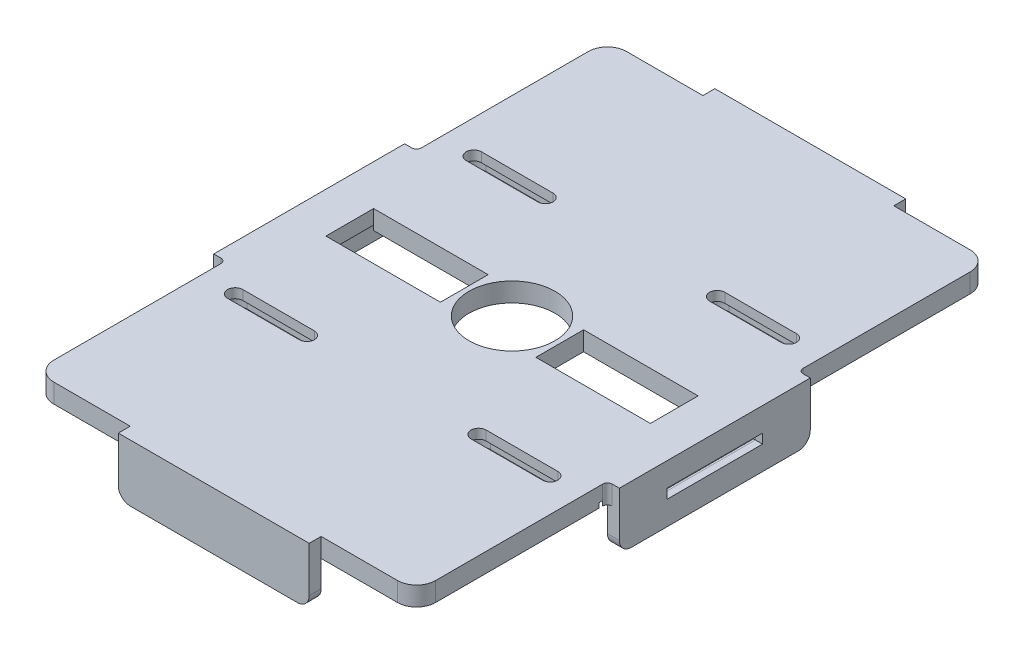
SolidWorks part; units mm, degrees
ref_plane "Front Plane" through (0, 0, 0) normal (0, 0, 1) x (1, 0, 0)
ref_plane "Top Plane" through (0, 0, 0) normal (0, 1, 0) x (1, 0, 0)
ref_plane "Right Plane" through (0, 0, 0) normal (1, 0, 0) x (0, 0, -1)
sketch "Sketch2" plane through (0, 40.2308, 0) normal (0, -1, 0) x (1, 0, 0)
  line L0 (-24.885, -26.4079) -> (-39.885, -26.4079) construction
  line L1 (-39.885, -23.2079) -> (-24.885, -23.2079) construction
  line L2 (-24.885, 23.5921) -> (-39.885, 23.5921) construction
  line L3 (-39.885, 26.7921) -> (-24.885, 26.7921) construction
  line L6 (-24.885, -26.4079) -> (-39.885, -26.4079)
  line L7 (-39.885, -23.2079) -> (-24.885, -23.2079)
  line L8 (-24.885, 23.5921) -> (-39.885, 23.5921)
  line L9 (-39.885, 26.7921) -> (-24.885, 26.7921)
  line L12 (-6.885, 34.7921) -> (-6.885, -34.4079) construction
  line L15 (26.115, 26.7921) -> (11.115, 26.7921)
  line L16 (11.115, 23.5921) -> (26.115, 23.5921)
  line L17 (26.115, -23.2079) -> (11.115, -23.2079)
  line L18 (11.115, -26.4079) -> (26.115, -26.4079)
  line L20 (-46.885, -59.8079) -> (33.115, -59.8079)
  line L21 (-46.885, -59.8079) -> (-46.885, 60.1921)
  line L22 (-46.885, 60.1921) -> (33.115, 60.1921)
  line L23 (33.115, -59.8079) -> (33.115, 60.1921)
  line L24 (-46.885, -59.8079) -> (33.115, 60.1921) construction
  line L25 (-46.885, 60.1921) -> (33.115, -59.8079) construction
  arc A0 (-6.885, 9.1921) -> (-6.885, -8.8079) centre (-6.885, 0.1921) ccw construction
  arc A1 (-24.885, -26.4079) -> (-24.885, -23.2079) centre (-24.885, -24.8079) ccw construction
  arc A2 (-39.885, -23.2079) -> (-39.885, -26.4079) centre (-39.885, -24.8079) ccw construction
  arc A3 (-24.885, 23.5921) -> (-24.885, 26.7921) centre (-24.885, 25.1921) ccw construction
  arc A4 (-39.885, 26.7921) -> (-39.885, 23.5921) centre (-39.885, 25.1921) ccw construction
  circle A7 centre (-6.885, 0.1921) radius 9
  arc A8 (-24.885, -26.4079) -> (-24.885, -23.2079) centre (-24.885, -24.8079) ccw
  arc A9 (-39.885, -23.2079) -> (-39.885, -26.4079) centre (-39.885, -24.8079) ccw
  arc A10 (-24.885, 23.5921) -> (-24.885, 26.7921) centre (-24.885, 25.1921) ccw
  arc A11 (-39.885, 26.7921) -> (-39.885, 23.5921) centre (-39.885, 25.1921) ccw
  arc A14 (-5.285, 33.1921) -> (-8.485, 33.1921) centre (-6.885, 33.1921) ccw construction
  arc A17 (26.115, 26.7921) -> (26.115, 23.5921) centre (26.115, 25.1921) cw
  arc A18 (11.115, 23.5921) -> (11.115, 26.7921) centre (11.115, 25.1921) cw
  arc A19 (26.115, -23.2079) -> (26.115, -26.4079) centre (26.115, -24.8079) cw
  arc A20 (11.115, -26.4079) -> (11.115, -23.2079) centre (11.115, -24.8079) cw
  dimension "D1" = 80
  dimension "D2" = 120
extrude "Boss-Extrude1" add sketch "Sketch2" along normal blind 4
fillet "Fillet1" radius 4 4 edges at (-46.885, 38.2308, 60.1921) (33.115, 38.2308, 60.1921) (33.115, 38.2308, -59.8079) (-46.885, 38.2308, -59.8079)
sketch "Sketch3" plane through (0, 36.2308, 0) normal (0, -1, 0) x (1, 0, 0)
  line L3 (-6.885, 60.1921) -> (-6.885, -59.8079) construction
  line L4 (29.115, 60.1921) -> (-42.885, 60.1921) construction
  line L5 (-42.885, -59.8079) -> (29.115, -59.8079) construction
  line L6 (-46.885, 0.1921) -> (33.115, 0.1921) construction
  line L7 (-26.885, 60.1921) -> (13.115, 60.1921)
  line L8 (-26.885, 60.1921) -> (-26.885, 62.6921)
  line L9 (-26.885, 62.6921) -> (13.115, 62.6921)
  line L10 (13.115, 60.1921) -> (13.115, 62.6921)
  line L11 (-26.885, 60.1921) -> (13.115, 62.6921) construction
  line L12 (-26.885, 62.6921) -> (13.115, 60.1921) construction
  line L17 (-46.885, 56.1921) -> (-46.885, -55.8079) construction
  line L18 (33.115, -55.8079) -> (33.115, 56.1921) construction
  point P12 (-6.885, 61.4421)
  dimension "D1" = 2.5
  dimension "D2" = 40
extrude "Boss-Extrude3" add sketch "Sketch3" along normal blind 8 and the other way blind 4
fillet "Fillet5" radius 2.5 2 edges at (-26.885, 28.2308, 61.4421) (13.115, 28.2308, 61.4421)
sketch "Sketch7"
  line L1 (16.885, -54.9298) -> (-3.115, -54.9298)
  line L2 (16.885, -54.9298) -> (16.885, -57.4298)
  line L3 (16.885, -57.4298) -> (-3.115, -57.4298)
  line L4 (-3.115, -54.9298) -> (-3.115, -57.4298)
  line L5 (16.885, -54.9298) -> (-3.115, -57.4298) construction
  line L6 (16.885, -57.4298) -> (-3.115, -54.9298) construction
  line L10 (6.885, 28.2308) -> (6.885, -140.5905) construction
  line L11 (24.385, 28.2308) -> (-10.615, 28.2308) construction
  point P0 (6.885, -56.1798)
  point P7 (6.885, -56.1798)
  dimension "D1" = 20
  dimension "D2" = 2.5
extrude "Cut-Extrude1" [suppressed] cut sketch "Sketch7" against normal up to next
ref_plane "Plane4" through (-6.885, 0, 0) normal (-1, 0, 0) x (0, 0, 1)
ref_plane "Plane5" through (0, 0, 0.1921) normal (0, 0, -1) x (-1, 0, 0)
fillet "Fillet10" [suppressed] radius 0.8
fillet "Fillet13" [suppressed] radius 1
mirror "Mirror6" about plane through (0, 0, 0.1921) normal (0, 0, -1) of "Fillet5", "Fillet13", "Boss-Extrude3", "Cut-Extrude1", "Fillet10"
fillet "Fillet14" [suppressed] radius 1
sketch "Sketch6" plane through (0, 36.2308, 0) normal (0, -1, 0) x (1, 0, 0)
  line L0 (-49.385, 20.1921) -> (-46.885, -19.8079) construction
  line L1 (-46.885, 20.1921) -> (-49.385, -19.8079) construction
  line L2 (-46.885, 56.1921) -> (-46.885, -55.8079) construction
  line L3 (-46.885, 0.1921) -> (33.115, 0.1921) construction
  line L8 (-49.385, -19.8079) -> (-46.885, -19.8079)
  line L9 (-49.385, -19.8079) -> (-49.385, 20.1921)
  line L10 (-46.885, -19.8079) -> (-46.885, 20.1921)
  line L11 (-49.385, 20.1921) -> (-46.885, 20.1921)
  point P2 (-48.135, 0.1921)
  dimension "D1" = 40
extrude "Boss-Extrude4" add sketch "Sketch6" along normal blind 8 and the other way blind 4
sketch "Sketch13" plane through (-49.385, 0, 0) normal (-1, 0, 0) x (0, 0, 1)
  line L0 (-19.8079, 34.2308) -> (20.1921, 34.2308) construction
  line L1 (-19.8079, 40.2308) -> (-19.8079, 28.2308) construction
  line L2 (20.1921, 40.2308) -> (20.1921, 28.2308) construction
  line L4 (-9.8079, 33.2308) -> (10.1921, 33.2308)
  line L5 (-9.8079, 33.2308) -> (-9.8079, 35.2308)
  line L6 (-9.8079, 35.2308) -> (10.1921, 35.2308)
  line L7 (10.1921, 33.2308) -> (10.1921, 35.2308)
  line L8 (-9.8079, 33.2308) -> (10.1921, 35.2308) construction
  line L9 (-9.8079, 35.2308) -> (10.1921, 33.2308) construction
  point P6 (0.1921, 34.2308)
  dimension "D1" = 20
  dimension "D2" = 2
extrude "Cut-Extrude6" cut sketch "Sketch13" against normal up to surface (2.5 mm away) up to face at (-46.885, 32.2308, 0.1921)
fillet "Fillet15" radius 1 4 edges at (-46.885, 34.2308, 10.1921) (-46.885, 35.2308, 0.1921) (-46.885, 33.2308, 0.1921) (-46.885, 34.2308, -9.8079)
mirror "Mirror31" about plane through (-6.885, 0, 0) normal (-1, 0, 0) of "Fillet15", "Boss-Extrude4", "Cut-Extrude6"
fillet "Fillet12" radius 1 4 edges at (-46.885, 38.2308, -19.8079) (-46.885, 38.2308, 20.1921) (33.115, 38.2308, 20.1921) (33.115, 38.2308, -19.8079)
fillet "Fillet9" radius 2.5 4 edges at (-48.135, 28.2308, -19.8079) (-48.135, 28.2308, 20.1921) (34.365, 28.2308, 20.1921) (34.365, 28.2308, -19.8079)
ref_plane "Plane6" through (3.115, 33.4577, -4.8079) normal (0, 1, 0) x (1, 0, 0)
sketch "Sketch15" plane through (0, 40.2308, 0) normal (0, 1, 0) x (1, 0, 0)
  line L1 (3.115, 4.8079) -> (27.115, 4.8079)
  line L2 (3.115, 4.8079) -> (3.115, -5.1921)
  line L3 (3.115, -5.1921) -> (27.115, -5.1921)
  line L4 (27.115, 4.8079) -> (27.115, -5.1921)
extrude "Cut-Extrude7" cut sketch "Sketch15" against normal up to surface (4 mm away) up to face at (18.615, 36.2308, 25.1921)
mirror "Mirror32" about plane through (-6.885, 0, 0) normal (-1, 0, 0) of "Cut-Extrude7"
sketch "Sketch16" plane through (-46.885, 0, 0) normal (-1, 0, 0) x (0, 0, 1)
  line L12 (-21.54, 36.2308) -> (21.9241, 36.2308)
  line L13 (-21.54, 36.2308) -> (-21.54, 37.2308)
  line L14 (-21.54, 37.2308) -> (21.9241, 37.2308)
  line L15 (21.9241, 36.2308) -> (21.9241, 37.2308)
extrude "Cut-Extrude8" cut sketch "Sketch16" against normal up to vertex (6 mm away)
mirror "Mirror34" about plane through (-6.885, 0, 0) normal (-1, 0, 0) of "Cut-Extrude8"
sketch "Sketch17" plane through (0, 36.2308, 0) normal (0, -1, 0) x (1, 0, 0)
  line L7 (-39.885, 22.6921) -> (-24.885, 22.6921)
  line L8 (-24.885, 27.6921) -> (-39.885, 27.6921)
  line L9 (-39.885, 22.6921) -> (-24.885, 22.6921)
  line L10 (-24.885, 27.6921) -> (-39.885, 27.6921)
  line L11 (-39.885, 23.5921) -> (-24.885, 23.5921)
  line L12 (-24.885, 26.7921) -> (-39.885, 26.7921)
  line L13 (-39.885, 23.5921) -> (-24.885, 23.5921)
  line L14 (-24.885, 26.7921) -> (-39.885, 26.7921)
  arc A7 (-24.885, 22.6921) -> (-24.885, 27.6921) centre (-24.885, 25.1921) ccw
  arc A8 (-39.885, 27.6921) -> (-39.885, 22.6921) centre (-39.885, 25.1921) ccw
  arc A9 (-24.885, 22.6921) -> (-24.885, 27.6921) centre (-24.885, 25.1921) ccw
  arc A10 (-39.885, 27.6921) -> (-39.885, 22.6921) centre (-39.885, 25.1921) ccw
  arc A11 (-24.885, 23.5921) -> (-24.885, 26.7921) centre (-24.885, 25.1921) ccw
  arc A12 (-39.885, 26.7921) -> (-39.885, 23.5921) centre (-39.885, 25.1921) ccw
  arc A13 (-24.885, 23.5921) -> (-24.885, 26.7921) centre (-24.885, 25.1921) ccw
  arc A14 (-39.885, 26.7921) -> (-39.885, 23.5921) centre (-39.885, 25.1921) ccw
  dimension "D1" = 0.9
  dimension "D2" = 0
extrude "Cut-Extrude9" cut sketch "Sketch17" against normal blind 2
mirror "Mirror35" about plane through (0, 0, 0.1921) normal (0, 0, -1) of "Cut-Extrude9" second plane through (-6.885, 0, 0) second plane normal (-1, 0, 0)
